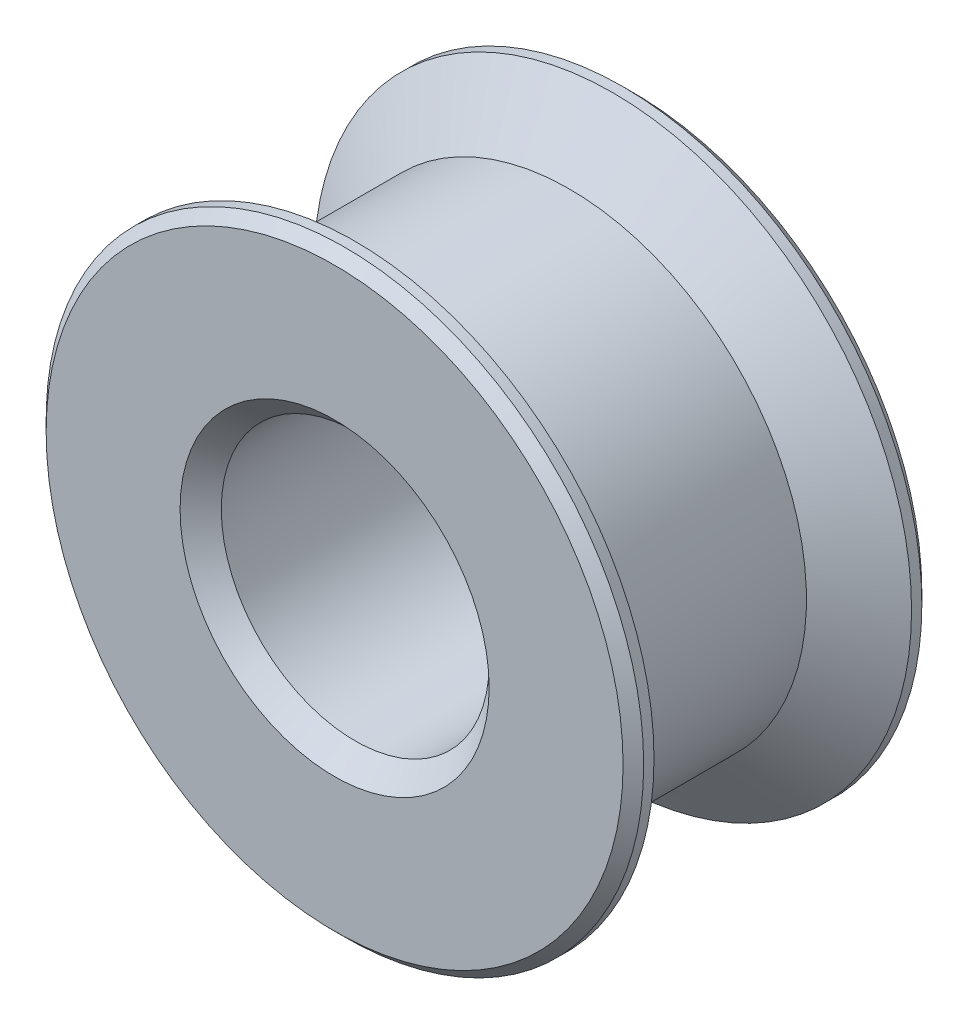
SolidWorks part; units mm, degrees
material "PLA"
ref_plane "Front Plane" through (0, 0, 0) normal (0, 0, 1) x (1, 0, 0)
ref_plane "Top Plane" through (0, 0, 0) normal (0, 1, 0) x (1, 0, 0)
ref_plane "Right Plane" through (0, 0, 0) normal (1, 0, 0) x (0, 0, -1)
sketch "Sketch1" plane through (0, 0, 0) normal (0, 0, 1) x (1, 0, 0)
  circle A0 centre (0, 0) radius 6.5
  circle A1 centre (0, 0) radius 11.5
  dimension "D1" = 13
  dimension "D2" = 5
extrude "Boss-Extrude1" add sketch "Sketch1" along normal mid plane 12.5
sketch "Sketch2" plane through (0, 0, 6.25) normal (0, 0, 1) x (1, 0, 0)
  circle A1 centre (0, 0) radius 6.5 construction
  circle A2 centre (0, 0) radius 14.5
  circle A3 centre (0, 0) radius 14.5
  circle A4 centre (0, 0) radius 6.5
  dimension "D1" = 3
extrude "Boss-Extrude2" add sketch "Sketch2" along normal blind 1
mirror "Mirror1" about plane through (0, 0, 0) normal (0, 0, 1) of "Boss-Extrude2"
chamfer "Chamfer1" distance 3 angle 35 2 edges at (11.5, 0, -6.25) (11.5, 0, 6.25) first distance on face at (11.5, 0, -6.25) first distance on face at (11.5, 0, 6.25)
chamfer "Chamfer2" distance 1 angle 45 2 edges at (6.5, 0, -7.25) (6.5, 0, 7.25)
chamfer "Chamfer3" distance 0.5 angle 45 2 edges at (14.5, 0, -7.25) (14.5, 0, 7.25)
